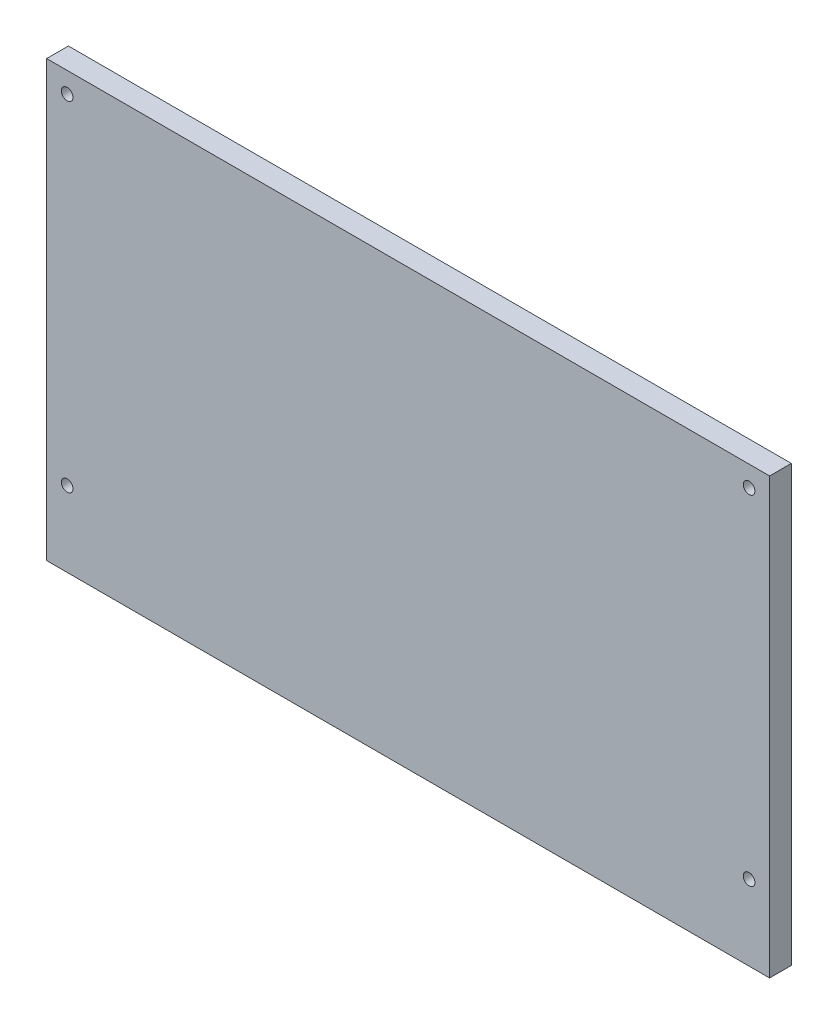
SolidWorks part; units mm, degrees
material "Acrylic (Medium-high impact)"
ref_plane "Front Plane" through (0, 0, 0) normal (0, 0, 1) x (1, 0, 0)
ref_plane "Top Plane" through (0, 0, 0) normal (0, 1, 0) x (1, 0, 0)
ref_plane "Right Plane" through (0, 0, 0) normal (1, 0, 0) x (0, 0, -1)
sketch "Sketch1" plane through (0, 0, 0) normal (0, 0, 1) x (1, 0, 0)
  line L1 (211.1756, 127) -> (0, 127)
  line L2 (211.1756, 127) -> (211.1756, 0)
  line L3 (211.1756, 0) -> (0, 0)
  line L4 (0, 127) -> (0, 0)
  line L5 (211.1756, 127) -> (0, 0) construction
  line L6 (211.1756, 0) -> (0, 127) construction
  point P0 (105.5878, 63.5)
  dimension "D1" = 127
  dimension "D2" = 211.1756
extrude "Boss-Extrude1" add sketch "Sketch1" along normal blind 6.35
hole_wizard "M3 Clearance Hole1" positions "Sketch2" profile "Sketch3" hole size "M3" standard "ANSI Metric" end condition through all
sketch "Sketch2" plane through (0, 0, 6.35) normal (0, 0, 1) x (1, 0, 0)
  line L0 (0, 127) -> (0, 0) construction
  line L1 (211.1756, 127) -> (0, 127) construction
  line L2 (211.1756, 0) -> (211.1756, 127) construction
  line L3 (0, 0) -> (211.1756, 0) construction
  point P0 (5.9944, 121.0056)
  point P2 (5.9944, 21.9964)
  point P4 (205.1812, 21.9964)
  point P6 (205.1812, 121.0056)
  dimension "D1" = 5.9944
  dimension "D2" = 5.9944
  dimension "D3" = 5.9944
  dimension "D4" = 21.9964
sketch "Sketch3" plane through (5.9944, 121.0056, 6.35) normal (1, 0, 0) x (0, -1, 0)
  line L0 (0, 0) -> (0, 6.35)
  line L1 (0, 6.35) -> (1.7, 6.35)
  line L2 (1.7, 6.35) -> (1.7, 0)
  line L5 (1.7, 0) -> (0, 0)
  line L11 (0, -6.35) -> (0, 107.95) construction
  dimension "Thru Hole Dia." = 3.4
  dimension "Thru Hole Depth" = 6.35
sketch "Sketch4" plane through (0, 0, 6.35) normal (0, 0, 1) x (1, 0, 0)
  line L0 (0, 127) -> (0, 0) construction
  line L1 (46.99, 107.95) -> (50.4952, 107.95)
  line L2 (46.99, 107.95) -> (46.99, 44.45)
  line L3 (46.99, 44.45) -> (50.4952, 44.45)
  line L4 (50.4952, 107.95) -> (50.4952, 44.45)
  line L5 (160.6804, 107.95) -> (164.1856, 107.95)
  line L6 (160.6804, 107.95) -> (160.6804, 44.45)
  line L7 (160.6804, 44.45) -> (164.1856, 44.45)
  line L8 (164.1856, 107.95) -> (164.1856, 44.45)
  line L9 (211.1756, 0) -> (211.1756, 127) construction
  line L10 (211.1756, 127) -> (0, 127) construction
  dimension "D1" = 3.5052
  dimension "D2" = 63.5
  dimension "D3" = 46.99
  dimension "D4" = 46.99
  dimension "D5" = 19.05
extrude "Cut-Extrude1" [suppressed] cut sketch "Sketch4" against normal through all
sketch "Sketch5" plane through (0, 0, 6.35) normal (0, 0, 1) x (1, 0, 0)
  line L0 (0, 36.1092) -> (76.2, 25.4)
  line L1 (0, 127) -> (0, 0) construction
  line L2 (76.2, 25.4) -> (134.9756, 25.4)
  line L3 (134.9756, 25.4) -> (211.1756, 36.1092)
  line L4 (211.1756, 0) -> (211.1756, 127) construction
  line L5 (211.1756, 36.1092) -> (211.1756, 0)
  line L6 (211.1756, 0) -> (0, 0)
  line L7 (0, 0) -> (0, 36.1092)
  dimension "D1" = 8
  dimension "D2" = 8
  dimension "D3" = 76.2
  dimension "D4" = 76.2
  dimension "D5" = 25.4
extrude "Cut-Extrude2" [suppressed] cut sketch "Sketch5" against normal through all
